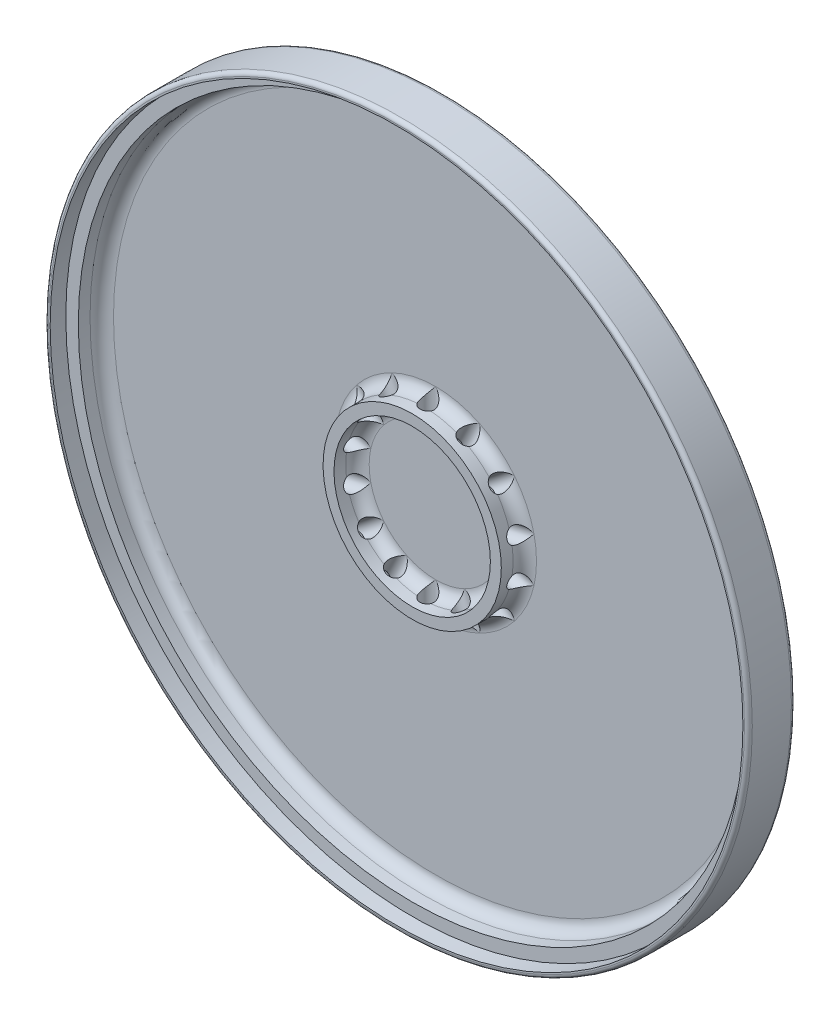
SolidWorks part; units mm, degrees
note: The reader was unsure of these and kept them because the rebuilt part matched: shared geometry of "Sketch1<3>", "Sketch1<4>", "Sketch1<5>".
ref_plane "Front Plane" through (0, 0, 0) normal (0, 0, 1) x (1, 0, 0)
ref_plane "Top Plane" through (0, 0, 0) normal (0, 1, 0) x (1, 0, 0)
ref_plane "Right Plane" through (0, 0, 0) normal (1, 0, 0) x (0, 0, -1)
sketch "Sketch1" plane through (0, 0, 0) normal (0, 0, 1) x (1, 0, 0)
  circle A0 centre (0, 0) radius 90
  circle A1 centre (0, 0) radius 88.6
  circle A2 centre (0, 0) radius 85.4
  circle A3 centre (0, 0) radius 20
  circle A4 centre (0, 0) radius 22.8
  dimension "D1" = 180
  dimension "D5" = 40
  dimension "D2" = 1.4
  dimension "D3" = 3.2
  dimension "D4" = 2.8
extrude "Boss-Extrude1" add sketch "Sketch1" against normal blind 2 contours A2 A4 | A1 A2 | A0 A1 | A3 | A4 A3
extrude "Boss-Extrude2" add sketch "Sketch1<3>" along normal blind 10 contours A0 A1
sketch "Sketch1<3>" plane through (0, 0, 0) normal (0, 0, 1) x (1, 0, 0) same geometry as "Sketch1"
extrude "Boss-Extrude3" add sketch "Sketch1<4>" along normal blind 6 contours A1 A2
sketch "Sketch1<4>" plane through (0, 0, 0) normal (0, 0, 1) x (1, 0, 0) same geometry as "Sketch1"
extrude "Boss-Extrude4" add sketch "Sketch1<5>" along normal blind 6 contours A4 A3
sketch "Sketch1<5>" plane through (0, 0, 0) normal (0, 0, 1) x (1, 0, 0) same geometry as "Sketch1"
sketch "Sketch2" plane through (0, 0, 0) normal (0, 1, 0) x (1, 0, 0)
  line L2 (-20, 0) -> (20, 0) construction
  circle A0 centre (0, -2) radius 2
  dimension "D1" = 4
extrude "Cut-Extrude3" cut sketch "Sketch2" against normal up to next and the other way up to next
fillet "Fillet1" radius 3 1 edges at (85.4, 0, 0)
fillet "Fillet2" radius 3 8 edges at (20, 0, 0) (-22.8, 0, 0) (0.2176, 22.799, 3.9881) (0.2198, 19.9988, 3.9879) (-20, 0, 0) (22.8, 0, 0) (0, -22.8, 4) (0, -20, 4)
fillet "Fillet3" radius 1 1 edges at (90, 0, -2)
fillet "Fillet4" radius 1 1 edges at (90, 0, 10)
pattern_circular "CirPattern1" count 7 over 360 about axis through (0, 0, 6) along (0, 0, -1) of "Cut-Extrude3"
